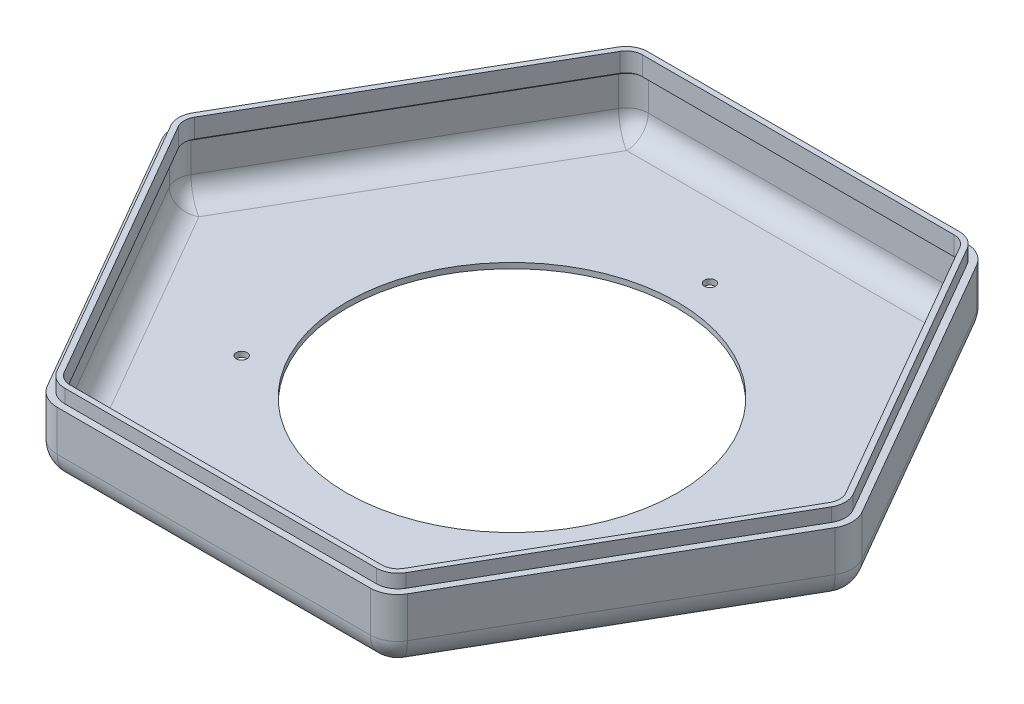
SolidWorks part; units mm, degrees
ref_plane "Alzado" through (0, 0, 0) normal (0, 0, 1) x (1, 0, 0)
ref_plane "Planta" through (0, 0, 0) normal (0, 1, 0) x (1, 0, 0)
ref_plane "Vista lateral" through (0, 0, 0) normal (1, 0, 0) x (0, 0, -1)
sketch "Croquis1" plane through (0, 0, 0) normal (0, 1, 0) x (1, 0, 0)
  line L1 (127.0171, 0) -> (63.5085, 110)
  line L2 (63.5085, 110) -> (-63.5085, 110)
  line L3 (-63.5085, 110) -> (-127.0171, 0)
  line L4 (-127.0171, 0) -> (-63.5085, -110)
  line L5 (-63.5085, -110) -> (63.5085, -110)
  line L6 (63.5085, -110) -> (127.0171, 0)
  circle A0 centre (0, 0) radius 110 construction
  dimension "D1" = 220
extrude "Saliente-Extruir1" add sketch "Croquis1" along normal blind 25
sketch "Croquis2" plane through (0, 25, 0) normal (0, 1, 0) x (1, 0, 0)
  line L0 (-62.0652, 107.5) -> (-124.1303, 0)
  line L1 (-124.1303, 0) -> (-62.0652, -107.5)
  line L2 (-62.0652, -107.5) -> (62.0652, -107.5)
  line L3 (62.0652, -107.5) -> (124.1303, 0)
  line L4 (124.1303, 0) -> (62.0652, 107.5)
  line L5 (62.0652, 107.5) -> (-62.0652, 107.5)
  line L6 (63.5085, -110) -> (127.0171, 0)
  line L7 (127.0171, 0) -> (63.5085, 110)
  line L8 (63.5085, 110) -> (-63.5085, 110)
  line L9 (-63.5085, 110) -> (-127.0171, 0)
  line L10 (-127.0171, 0) -> (-63.5085, -110)
  line L11 (-63.5085, -110) -> (63.5085, -110)
  line L12 (63.5085, -110) -> (127.0171, 0) construction
  line L13 (127.0171, 0) -> (63.5085, 110) construction
  line L14 (63.5085, 110) -> (-63.5085, 110) construction
  line L15 (-63.5085, 110) -> (-127.0171, 0) construction
  line L16 (-127.0171, 0) -> (-63.5085, -110) construction
  line L17 (-63.5085, -110) -> (63.5085, -110) construction
  line L18 (-60.9105, 105.5) -> (-121.8209, 0)
  line L19 (-121.8209, 0) -> (-60.9105, -105.5)
  line L20 (-60.9105, -105.5) -> (60.9105, -105.5)
  line L21 (60.9105, -105.5) -> (121.8209, 0)
  line L22 (121.8209, 0) -> (60.9105, 105.5)
  line L23 (60.9105, 105.5) -> (-60.9105, 105.5)
  dimension "D1" = 0
  dimension "D2" = 2.5
  dimension "D3" = 2
extrude "Saliente-Extruir2" add sketch "Croquis2" along normal blind 5
fillet "Redondeo1" radius 10 12 edges at (95.2628, 0, -55) (0, 0, -110) (-95.2628, 0, -55) (-95.2628, 0, 55) (0, 0, 110) (95.2628, 0, 55) (-63.5085, 12.5, 110) (63.5085, 12.5, 110) (127.0171, 12.5, 0) (63.5085, 12.5, -110) (-63.5085, 12.5, -110) (-127.0171, 12.5, 0)
fillet "Redondeo2" radius 8 6 edges at (-62.0652, 27.5, 107.5) (-124.1303, 27.5, 0) (-62.0652, 27.5, -107.5) (62.0652, 27.5, -107.5) (124.1303, 27.5, 0) (62.0652, 27.5, 107.5)
fillet "Redondeo3" radius 6 6 edges at (-121.8209, 27.5, 0) (-60.9105, 27.5, -105.5) (60.9105, 27.5, -105.5) (121.8209, 27.5, 0) (60.9105, 27.5, 105.5) (-60.9105, 27.5, 105.5)
shell "Vaciado1" thickness 2 removed face at (0, 25, 0)
chamfer "Chaflán1" distance 2 angle 45 12 edges at (93.5307, 23, -54) (61.735, 23, -106.9282) (123.4701, 23, 0) (0, 23, -108) (93.5307, 23, 54) (-61.735, 23, -106.9282) (61.735, 23, 106.9282) (-93.5307, 23, -54) (0, 23, 108) (-123.4701, 23, 0) (-61.735, 23, 106.9282) (-93.5307, 23, 54)
sketch "Croquis3" plane through (0, 2, 0) normal (0, 1, 0) x (1, 0, 0)
  line L0 (0, 0) -> (0, 73) construction
  line L1 (0, 73) -> (-63.2199, -36.5) construction
  line L2 (-63.2199, -36.5) -> (63.2199, -36.5) construction
  line L3 (63.2199, -36.5) -> (0, 73) construction
  line L4 (0, 0) -> (63.2199, -36.5) construction
  circle A0 centre (0, 0) radius 61
  circle A1 centre (0, 73) radius 2
  circle A2 centre (63.2199, -36.5) radius 2
  circle A3 centre (-63.2199, -36.5) radius 2
  point P9 (0, -36.5)
  dimension "D1" = 73
  dimension "D2" = 4
  dimension "D3" = 122
extrude "Cortar-Extruir1" cut sketch "Croquis3" against normal up to next
